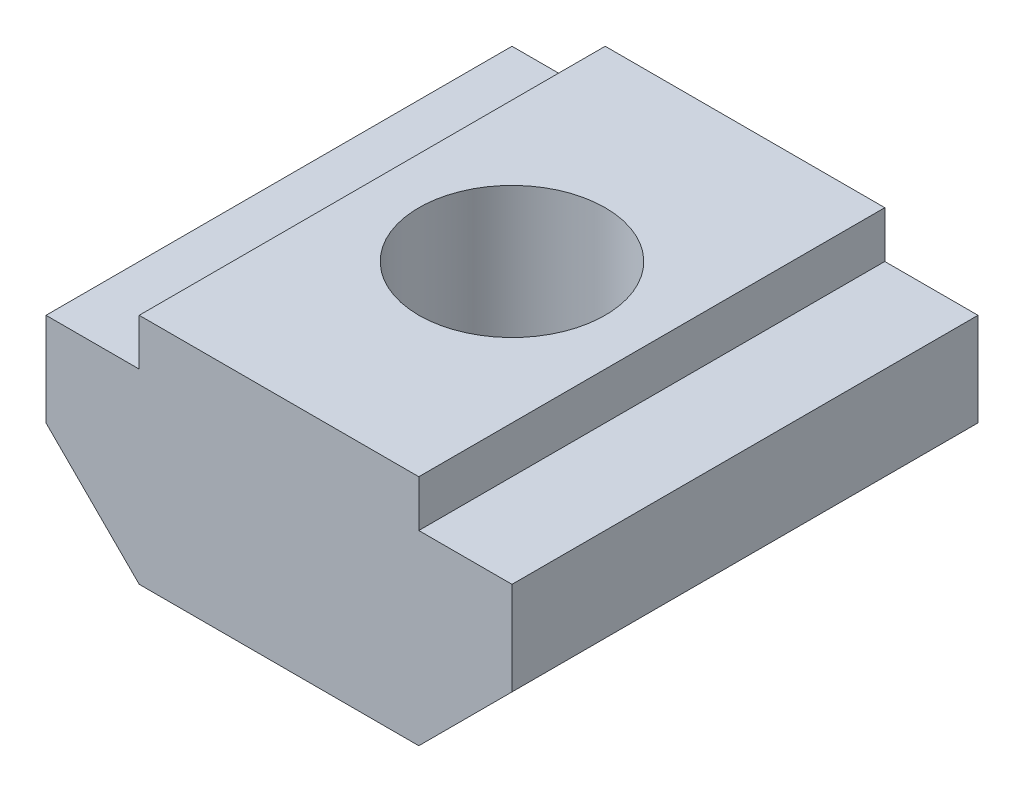
SolidWorks part; units mm, degrees
ref_plane "Plano frontal" through (0, 0, 0) normal (0, 0, 1) x (1, 0, 0)
ref_plane "Plano superior" through (0, 0, 0) normal (0, 1, 0) x (1, 0, 0)
ref_plane "Plano direito" through (0, 0, 0) normal (1, 0, 0) x (0, 0, -1)
sketch "Esboço1" plane through (0, 0, 0) normal (0, 0, 1) x (1, 0, 0)
  line L0 (-3, 0) -> (3, 0)
  line L1 (0, 0) -> (0, -1) construction
  line L2 (-5, -1) -> (-3, -1)
  line L3 (-3, 0) -> (-3, -1)
  line L4 (3, 0) -> (3, -1)
  line L5 (3, -1) -> (5, -1)
  line L6 (-5, -1) -> (-5, -5)
  line L7 (-5, -5) -> (5, -5)
  line L8 (5, -5) -> (5, -1)
  point P4 (0, 0)
  point P10 (0, -1)
  dimension "D1" = 6
  dimension "D2" = 10
  dimension "D3" = 1
  dimension "D4" = 4
extrude "Ressalto-extrusão1" add sketch "Esboço1" along normal blind 10
chamfer "Chanfro1" distance 2 angle 45 2 edges at (-5, -5, 5) (5, -5, 5)
sketch "Esboço2" plane through (0, 0, 0) normal (0, 1, 0) x (1, 0, 0)
  line L0 (0, 0) -> (0, -10) construction
  line L1 (3, -10) -> (-3, -10) construction
  circle A0 centre (0, -5) radius 2
  dimension "D1" = 4
extrude "Corte-extrusão1" cut sketch "Esboço2" against normal up to surface (5 mm away) up to face at (0, -5, 5)
ref_plane "Plano1" through (0, 0, 0) normal (-1, 0, 0) x (0, 0, 1)
ref_plane "Plano2" through (0, 0, 5) normal (0, 0, -1) x (-1, 0, 0)
